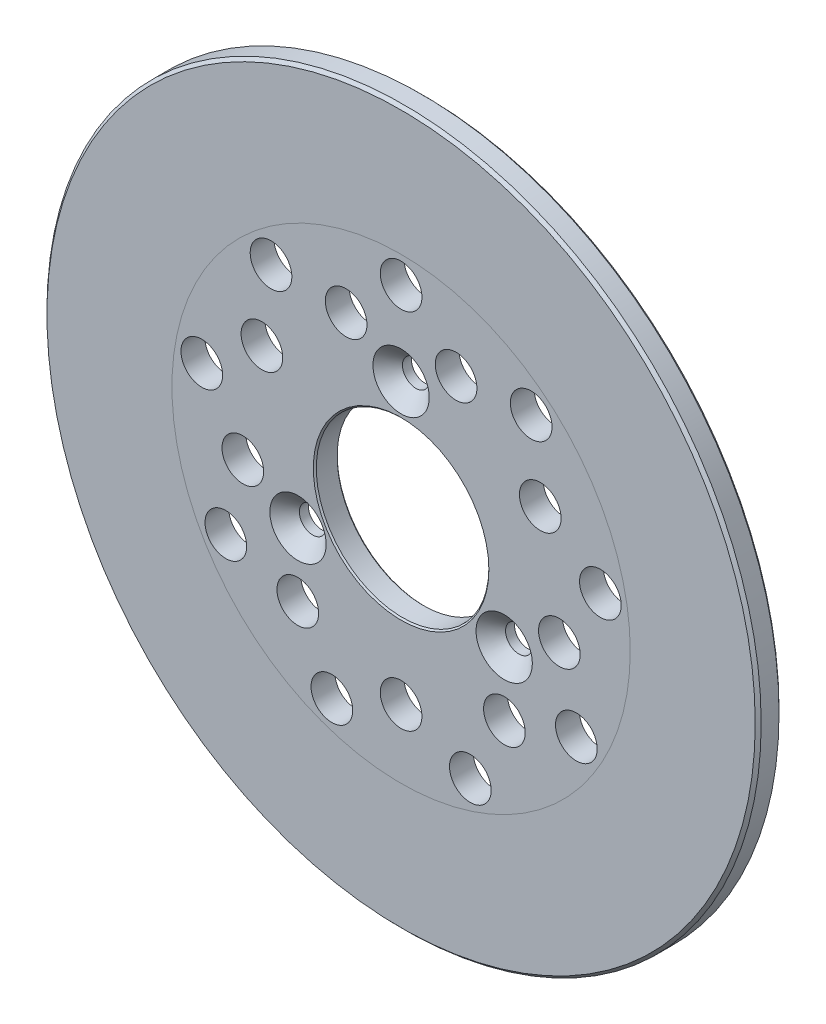
SolidWorks part; units mm, degrees
ref_plane "Přední rovina" through (0, 0, 0) normal (0, 0, 1) x (1, 0, 0)
ref_plane "Horní rovina" through (0, 0, 0) normal (0, 1, 0) x (1, 0, 0)
ref_plane "Pravá rovina" through (0, 0, 0) normal (1, 0, 0) x (0, 0, -1)
sketch "Skica1" plane through (0, 0, 0) normal (0, 0, 1) x (1, 0, 0)
  circle A0 centre (0, 0) radius 120
  circle A1 centre (0, 0) radius 29
  dimension "D1" = 240
  dimension "D2" = 58
extrude "Přidat vysunutím1" add sketch "Skica1" along normal blind 8
hole_wizard "Kuželové zahloubení pro M8 šrouby s zápustnou hlavou s vnitřním šestihranem1" positions "Skica3" profile "Skica2" countersink size "M8" standard "ISO"
sketch "Skica3" plane through (0, 0, 8) normal (0, 0, 1) x (1, 0, 0)
  line L0 (0, -8.5827) -> (0, 68.9683) construction
  line L2 (0, 0) -> (60.7971, -35.1012) construction
  line L5 (0, 0) -> (-56.2798, -32.4932) construction
  circle A0 centre (0, 0) radius 40 construction
  point P0 (0, 40)
  point P2 (34.641, -20)
  point P4 (-34.641, -20)
  dimension "D1" = 80
  dimension "D2" = 120
  dimension "D3" = 120
sketch "Skica2" plane through (0, 40, 8) normal (1, 0, 0) x (0, -1, 0)
  line L0 (0, 0) -> (0, 10.7039)
  line L1 (0, 10.7039) -> (4.5, 8)
  line L2 (4.5, 8) -> (4.5, 4.96)
  line L3 (4.5, 4.96) -> (9.46, 0)
  line L5 (9.46, 0) -> (0, 0)
  line L6 (-4.5, 4.96) -> (-9.46, 0) construction
  line L10 (0, 10.7039) -> (-4.5, 8) construction
  line L11 (0, -6.35) -> (0, 107.95) construction
  dimension "Průměr díry" = 9
  dimension "Hloubka díry" = 8
  dimension "Průměr blíz. kuž. zahloubení" = 18.92
  dimension "Úhel blíz. kuž. zahloubení" = 90
  dimension "Úhel vrtání" = 118
chamfer "Zkosení1" distance 0.5 angle 45 1 edges at (29, 0, 0)
chamfer "Zkosení2" distance 0.5 angle 45 1 edges at (29, 0, 8)
sketch "Skica4" plane through (0, 0, 8) normal (0, 0, 1) x (1, 0, 0)
  line L0 (0, 0) -> (18.4691, 50.7434) construction
  line L1 (0, -14.5117) -> (0, 81.2415) construction
  circle A0 centre (0, 0) radius 54 construction
  circle A1 centre (18.4691, 50.7434) radius 7
  dimension "D1" = 108
  dimension "D2" = 14
  dimension "D3" = 20
extrude "Odebrat vysunutím1" cut sketch "Skica4" against normal through all
ref_axis "Osa1" through (0, 0, 7.5) along (0, 0, -1)
pattern_circular "Kruhové pole1" count 9 over 360 about axis through (0, 0, 7.5) along (0, 0, -1) of "Odebrat vysunutím1"
sketch "Skica5" plane through (0, 0, 8) normal (0, 0, 1) x (1, 0, 0)
  circle A0 centre (0, 0) radius 77
  dimension "D1" = 154
split line "Rozdělovací křivka1"
chamfer "Zkosení3" distance 1 angle 45 2 edges at (120, 0, 0) (120, 0, 8)
sketch "Skica6" plane through (0, 0, 8) normal (0, 0, 1) x (1, 0, 0)
  line L0 (0, -8.2477) -> (0, 68) construction
  circle A0 centre (0, 68) radius 7
  dimension "D1" = 14
  dimension "D2" = 68
extrude "Odebrat vysunutím2" cut sketch "Skica6" against normal through all
pattern_circular "Kruhové pole2" count 9 over 360 about axis through (0, 0, 7.5) along (0, 0, -1) of "Odebrat vysunutím2"
